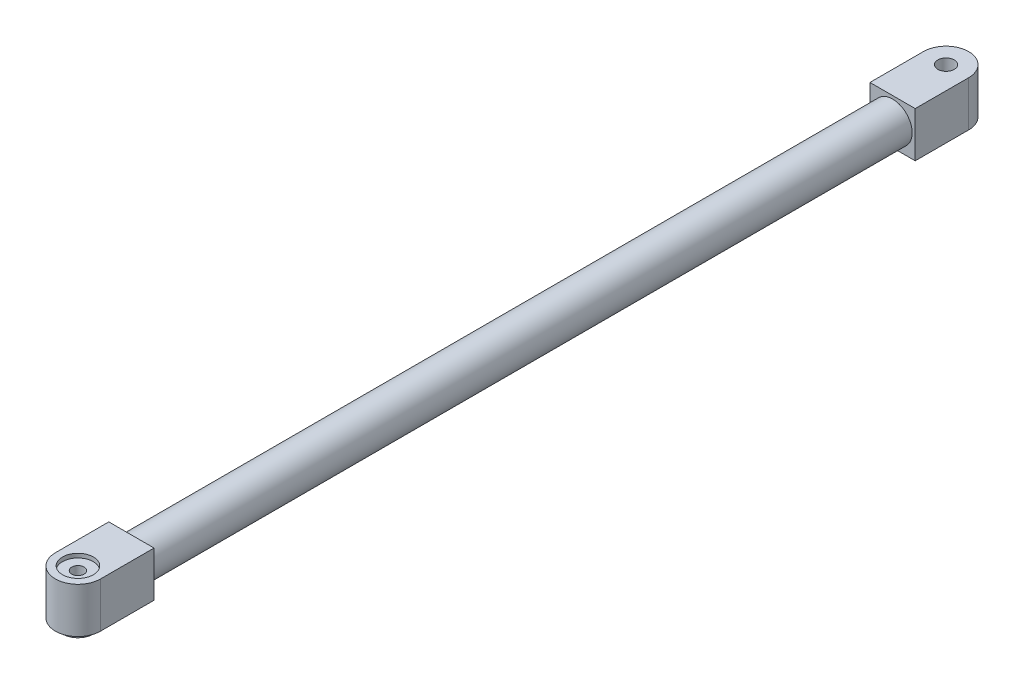
SolidWorks part; units mm, degrees
note: The reader was unsure of these and kept them because the rebuilt part matched: shared geometry of "Sketch2<2>".
ref_plane "Front Plane" through (0, 0, 0) normal (0, 0, 1) x (1, 0, 0)
ref_plane "Top Plane" through (0, 0, 0) normal (0, 1, 0) x (1, 0, 0)
ref_plane "Right Plane" through (0, 0, 0) normal (1, 0, 0) x (0, 0, -1)
other "Center of Mass"
sketch "Sketch1" plane through (0, 0, 0) normal (0, 0, 1) x (1, 0, 0)
  circle A0 centre (0, 0) radius 9.525
  circle A1 centre (0, 0) radius 6.2738
  dimension "D1" = 19.05
  dimension "D2" = 3.2512
extrude "Boss-Extrude1" add sketch "Sketch1" along normal blind 400
ref_plane "Plane1" through (0, 0, 200) normal (0, 0, -1) x (-1, 0, 0)
sketch "Sketch2" plane through (0, 0, 0) normal (0, 0, -1) x (-1, 0, 0)
  line L0 (-11, 11) -> (11, -11) construction
  line L1 (-11, 11) -> (11, 11)
  line L2 (-11, 11) -> (-11, -11)
  line L3 (-11, -11) -> (11, -11)
  line L4 (11, 11) -> (11, -11)
  circle A0 centre (0, 0) radius 9.525 construction
  circle A1 centre (0, 0) radius 9.525
  point P7 (0, 0)
  dimension "D1" = 22
extrude "Boss-Extrude2" add sketch "Sketch2" against normal blind 15 separate body
extrude "Boss-Extrude3" add sketch "Sketch2<2>" along normal blind 2 separate body contours L1 L4 L3 L2
sketch "Sketch2<2>" plane through (0, 0, 0) normal (0, 0, -1) x (-1, 0, 0) same geometry as "Sketch2"
combine bodies "Combine1" operation type add bodies to combine 102 103
sketch "Sketch3" plane through (0, -11, 0) normal (0, -1, 0) x (1, 0, 0)
  line L0 (11, -2) -> (11, -11)
  line L1 (11, -2) -> (-11, -2)
  line L2 (-11, -2) -> (-11, -11)
  line L3 (11, 0) -> (-11, 0) construction
  arc A0 (11, -11) -> (-11, -11) centre (0, -11) ccw construction
  arc A1 (-11, -11) -> (11, -11) centre (0, -11) ccw
  circle A2 centre (0, -11) radius 4
  dimension "D1" = 8
extrude "Boss-Extrude4" add sketch "Sketch3" against normal up to surface (22 mm away) up to face at (0, 11, 6.5)
mirror "Mirror7" about plane through (0, 0, 200) normal (0, 0, -1) of bodies 105
sketch "Sketch4" plane through (0, -11, 0) normal (0, -1, 0) x (1, 0, 0)
  circle A0 centre (0, 411) radius 7.5
  dimension "D1" = 15
extrude "Cut-Extrude1" cut sketch "Sketch4" against normal up to next (22 mm away)
sketch "Sketch6" plane through (0, -11, 0) normal (0, -1, 0) x (1, 0, 0)
  circle A0 centre (0, 411) radius 7.5 construction
  circle A1 centre (0, 411) radius 7.5
extrude "Boss-Extrude5" add sketch "Sketch6" against normal blind 20 and the other way blind 3 separate body
sketch "Sketch8" plane through (0, -14, 0) normal (0, -1, 0) x (1, 0, 0)
  circle A0 centre (0, 411) radius 3
  dimension "D1" = 6
extrude "Cut-Extrude2" cut sketch "Sketch8" against normal up to next (23 mm away)
